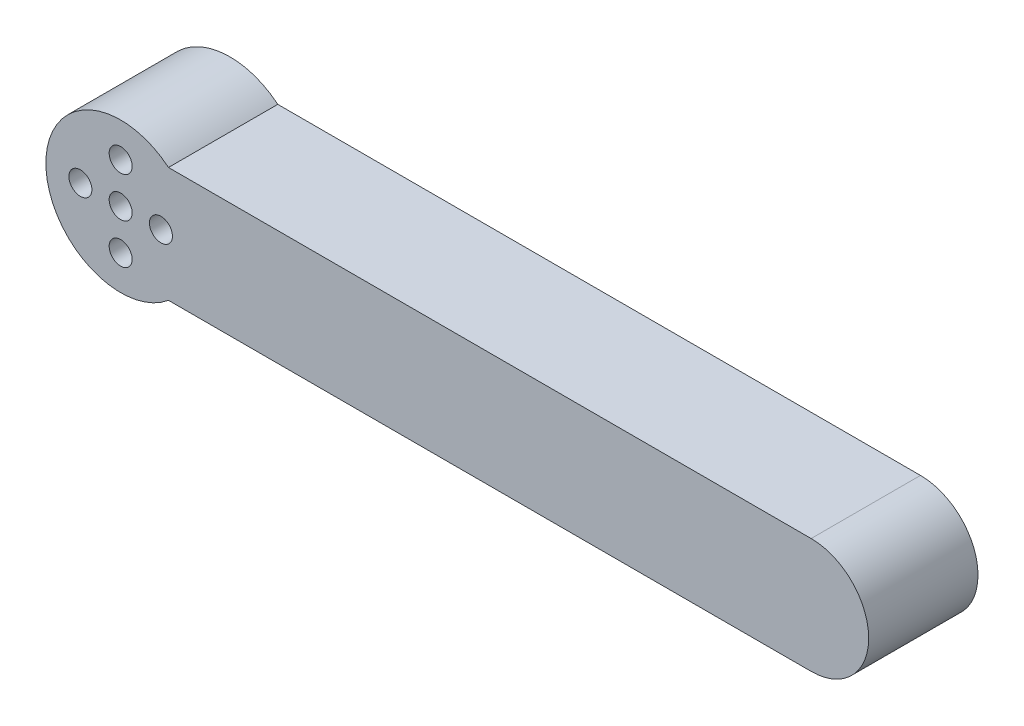
SolidWorks part; units mm, degrees
material "PLA"
ref_plane "Front Plane" through (0, 0, 0) normal (0, 0, 1) x (1, 0, 0)
ref_plane "Top Plane" through (0, 0, 0) normal (0, 1, 0) x (1, 0, 0)
ref_plane "Right Plane" through (0, 0, 0) normal (1, 0, 0) x (0, 0, -1)
sketch "Sketch1" plane through (0, 0, 0) normal (0, 0, 1) x (1, 0, 0)
  circle A0 centre (0, 0) radius 13
  dimension "D1" = 26
extrude "Elbow Boss" add sketch "Sketch1" along normal blind 19
sketch "Sketch2" plane through (0, 0, 0) normal (0, 0, 1) x (1, 0, 0)
  line L0 (0, 0) -> (120, 0) construction
  line L1 (0, 10) -> (120, 10)
  line L2 (0, -10) -> (120, -10)
  arc A0 (0, 10) -> (0, -10) centre (0, 0) ccw
  arc A1 (120, -10) -> (120, 10) centre (120, 0) ccw
  point P3 (60, 0)
  dimension "D1" = 120
  dimension "D2" = 20
extrude "Bar" add sketch "Sketch2" along normal blind 19
sketch "Sketch3" plane through (0, 0, 0) normal (0, 0, -1) x (-1, 0, 0)
  circle A0 centre (0, 0) radius 10.1
  dimension "D1" = 20.2
extrude "Cut-Extrude1" cut sketch "Sketch3" against normal blind 4 and the other way through all
sketch "Sketch4" plane through (0, 0, 4) normal (0, 0, -1) x (-1, 0, 0)
  circle A0 centre (0, 0) radius 4.25
  dimension "D1" = 8.5
extrude "Cut-Extrude2" cut sketch "Sketch4" against normal blind 2.6
sketch "Sketch5" plane through (0, 0, 19) normal (0, 0, 1) x (1, 0, 0)
  circle A0 centre (0, 0) radius 2
  dimension "D1" = 4
extrude "Cut-Extrude3" cut sketch "Sketch5" against normal blind 10
sketch "Sketch6" plane through (0, 0, 19) normal (0, 0, 1) x (1, 0, 0)
  line L0 (0, 0) -> (73.1562, 0) construction
  circle A0 centre (7, 0) radius 2
  point P5 (0, 0)
  point P6 (10.1314, 0)
  dimension "D1" = 4
  dimension "D2" = 7
extrude "Cut-Extrude4" cut sketch "Sketch6" against normal blind 13
sketch "Sketch7" plane through (0, 0, 4) normal (0, 0, -1) x (-1, 0, 0)
  line L0 (0, 0) -> (-49.2438, 0) construction
  circle A0 centre (-7, 0) radius 1.1
  point P2 (-7, 0)
  dimension "D2" = 7
  dimension "D1" = 2.2
extrude "Cut-Extrude5" cut sketch "Sketch7" against normal through all
ref_axis "Elbow Axis" through (0, 0, 9) along (0, 0, 1)
pattern_circular "CirPattern1" count 4 over 360 about axis through (0, 0, 9) along (0, 0, 1) of "Cut-Extrude4", "Cut-Extrude5"
ref_axis "Wrist Axis" through (120, 0, 19) along (0, 0, -1)
equation "\"L1\"= 120mm'Upper arm"
equation "\"L3\"= 75mm'Wrist→TCP"
equation "\"h0\"= 75mm'Shoulder height"
equation "\"t_link\"= 3mm'Link plate thickness"
equation "\"t_bracket\"= 4mm'Bracket thickness"
equation "\"d_pin\"= 4mm'Pin diameter (M4)"
equation "\"c_fit\"= 0.2mm'Nominal clearance - measured PLA 2026-10-01"
equation "\"L2\"= 120mm'Forearm"
equation "\"c_fit_pivot\"= \"c_fit\" + 0.05mm'Gripper pivot clearance - chosen 0.25 mm 2026-10-01"
equation "\"d_pin_gripper\"= 3mm'Gripper pivot diameter"
equation "\"w_link\"= 20mm'Link plate depth (bending direction)"
equation "\"w_gap\"= 20mm'Twin-plate gap - provisional, set by elbow servo mount"
equation "\"d_boss\"= 13mm'MG996R output boss dia - from downloaded model, verify with calipers"
equation "\"c_boss\"= 1mm'Radial clearance around servo boss"
equation "\"d_servo_hole\"= \"d_boss\" + 2 * \"c_boss\"'Plate clearance hole for servo boss (15 mm)"
equation "\"t_rim\"= 9.5mm'Min material around servo hole (M3 hole + 3 mm webs each side)"
equation "\"w_link_end\"= \"d_servo_hole\" + 2 * \"t_rim\"'Link plate end width at servo end (34 mm)"
equation "\"d_hole_m3\"= \"d_pin_gripper\" + \"c_fit\"'M3 bolt clearance hole (spacer and adapter bolts)"
equation "\"d_hole_pivot\"= \"d_pin\" + \"c_fit_pivot\"'M4 pivot hole where the pin rotates (4.25 mm)"
equation "\"d_horn\"= 20mm'Horn disc diameter (circular horn) - from MG996R model"
equation "\"t_horn\"= 2.3mm'Horn disc thickness"
equation "\"g_horn\"= 2.2mm'Gap from horn disc to plate 2 inner face - from MockShoulder"
equation "\"d_horn_pocket\"= \"d_horn\" + \"c_fit\"'Adapter pocket for horn disc (20.2 mm)"
equation "\"h_horn_pocket\"= \"g_horn\" + \"t_horn\"'Pocket depth from adapter plate-2 face (4.5 mm)"
equation "\"d_horn_screw_cb\"= 8.5mm'Recess for horn centre-screw head (head is 7.5 mm)"
equation "\"h_horn_screw_cb\"= 2.6mm'Recess depth (head is 2.35 mm tall)"
equation "\"d_adapter\"= 26mm'Horn adapter outer diameter"
equation "\"h_adapter\"= \"w_gap\"'Adapter length, fills the plate gap"
equation "\"t_adapter_floor\"= 2mm'Floor under horn disc that the horn screws pass through"
equation "\"d_horn_screw_hole\"= 2.2mm'Clearance for M2 self-tapper through the floor"
equation "\"r_horn_screw\"= 7mm'Horn screw hole radius (14 mm square pattern)"
equation "\"d_access\"= 4mm'Access bore for the M2 screws from the plate-1 side"
equation "\"d_insert_m3\"= 4mm'Hole for M3 heat-set insert - HZYUEGOU M3 inserts are 4.2 OD, hole 4.0; open to 4.1 if too tight"
equation "\"h_insert_m3\"= 6mm'Insert hole depth"
equation "\"x_adapter_bolt\"= 6mm'Adapter bolt offset from pin, along the arm toward its middle"
equation "\"y_adapter_bolt\"= 5mm'Adapter bolt offset from pin, across the arm (+/-)"
equation "\"d_csk_m3\"= 6.4mm'Countersink diameter in plate 1 for M3 flat head (90 deg)"
equation "\"h_pin_bore\"= 10mm'M4 pin engagement depth in the adapter"
equation "\"c_win\"= 0.3mm'Servo window clearance per side in bracket wall A - starting value, tune after a test print"
equation "\"l_servo\"= 40.9mm'MG996R case length without ears - from the model"
equation "\"w_servo\"= 20mm'MG996R case width - from the model"
equation "\"r_servo_short\"= 10mm'Shaft axis to the short end of the case - from the model"
equation "\"r_servo_long\"= \"l_servo\" - \"r_servo_short\"'Shaft axis to the long end of the case (30.9 mm)"
equation "\"l_ear_holes\"= 48.6mm'MG996R ear hole (keyhole slot) spacing along the case - from the model"
equation "\"w_ear_holes\"= 10mm'MG996R ear hole spacing across the case - from the model"
equation "\"a_ear\"= 8.2mm'Servo ear seating face to plate-2 outer face - from MockShoulder (ear face incl. 0.2 edge round)"
equation "\"l_window\"= \"l_servo\" + 2 * \"c_win\"'Wall A window length (41.5 mm)"
equation "\"w_window\"= \"w_servo\" + 2 * \"c_win\"'Wall A window width (20.6 mm)"
equation "\"g_wall_a\"= \"a_ear\" - \"t_bracket\"'Gap behind wall A to plate 2 (4.2 mm) - ear screw heads sit here"
equation "\"g_wall_b\"= 1mm'Plate 1 outer face to wall B - thrust washer"
equation "\"d_axis_turret\"= 34mm'Shoulder axis to turret mounting face - PLACEHOLDER until the turret is designed"
equation "\"t_foot\"= 6mm'Bracket foot thickness"
equation "\"h_wall_top\"= 41.5mm'Wall A top above the shoulder axis (long-end ear holes + 4 mm)"
equation "\"w_wall\"= 30mm'Bracket wall A and B width"
equation "\"w_foot\"= 50mm'Bracket foot width across the walls"
equation "\"t_boss_b\"= 4mm'Extra thickness of the pin boss on the outside of wall B"
equation "\"d_boss_b\"= 12mm'Pin boss diameter on wall B"
equation "\"r_wall_corner\"= 10mm'Wall A top corner radius"
equation "\"l_notch\"= 6.4mm'Ear rib notch length past each end of the wall A window - from the model"
equation "\"w_notch\"= 1.66mm'Ear rib notch width (1.0 rib + 0.33 each side)"
equation "\"l_foot_back\"= 11.6mm'Bracket foot overhang behind wall A outer face"
equation "\"l_foot_front\"= 11mm'Bracket foot overhang past wall B outer face"
equation "\"w_turret_holes\"= 40mm'Turret bolt pattern across the foot (X)"
equation "\"e_turret_hole\"= 4.8mm'Foot insert hole centre to foot end (2.8 mm plastic with d_insert_m3 = 4.0)"
equation "\"z_wall_b_out\"= \"a_ear\" + 2 * \"t_link\" + \"w_gap\" + \"g_wall_b\" + \"t_bracket\"'Wall B outer face from wall A outer face (39.2 mm)"
equation "\"z_turret_hole\"= \"z_wall_b_out\" + \"l_foot_front\" - \"e_turret_hole\"'Upper foot insert holes from wall A outer face (45.4 mm); lower pair mirrors about the foot centre"
equation "\"r_foot_fillet\"= 4mm'Wall-to-foot fillet radius"
equation "\"c_side\"= 0.5mm'Forearm running clearance to each upper-arm plate at the elbow"
equation "\"w_forearm\"= \"w_gap\" - 2 * \"c_side\"'Solid forearm width along the elbow axis (19 mm)"
equation "\"h_forearm\"= \"w_link\"'Forearm depth in the arm plane (20 mm, same as the plates)"
equation "\"h_horn_pocket_fa\"= \"g_horn\" - \"c_side\" + \"t_horn\"'Elbow horn pocket depth from the forearm plate-1 face (4.0 mm)"
equation "\"h_dowel_fa\"= 10mm'Elbow dowel depth in the forearm - press fit, hole = d_pin"
equation "\"l_dowel_elbow\"= \"h_dowel_fa\" + \"c_side\" + \"t_link\"'Elbow dowel length, flush with plate 2 outer face (13.5 mm)"
equation "\"r_mount_bolt\"= \"L1\" / 4'Elbow axis to the upper-arm spacer holes on the shoulder side (30 mm) - elbow servo mount bolts through these"
equation "\"h_standoff\"= \"g_wall_a\"'Elbow mount standoffs, wall to plate 1 outer face (4.2 mm)"
equation "\"d_standoff\"= 7mm'Elbow mount standoff diameter, same as the upper-arm spacers"
equation "\"e_mount\"= 5mm'Elbow mount wall end past the standoff hole centres (3.4 mm plastic outside the hole)"
equation "\"l_mount_back\"= \"r_mount_bolt\" + \"e_mount\"'Elbow mount wall end toward the shoulder, from the elbow axis (35 mm)"
equation "\"l_mount_bolt\"= \"t_bracket\" + \"h_standoff\" + 2 * \"t_link\" + \"w_gap\"'Grip of the two spacer bolts through the elbow mount (34.2 mm) - M3x40 + nut"
equation "\"D1@Sketch1\"=\"d_adapter\""
equation "\"D1@Elbow Boss\" = \"w_forearm\""
equation "\"D1@Sketch2\"=\"L2\""
equation "\"D2@Sketch2\"=\"h_forearm\""
equation "\"D1@Bar\" = \"w_forearm\""
equation "\"D1@Sketch3\"=\"d_horn_pocket\""
equation "\"D1@Cut-Extrude1\"=\"h_horn_pocket_fa\""
equation "\"D1@Sketch4\"=\"d_horn_screw_cb\""
equation "\"D1@Cut-Extrude2\"=\"h_horn_screw_cb\""
equation "\"D1@Sketch5\"=\"d_pin\""
equation "\"D1@Cut-Extrude3\"=\"h_dowel_fa\""
equation "\"D1@Sketch6\"=\"d_access\""
equation "\"D2@Sketch6\"=\"r_horn_screw\""
equation "\"D1@Cut-Extrude4\"=\"w_forearm\"-\"h_horn_pocket_fa\"-\"t_adapter_floor\""
equation "\"D1@Sketch7\"=\"d_horn_screw_hole\""
equation "\"D2@Sketch7\"=\"r_horn_screw\""
